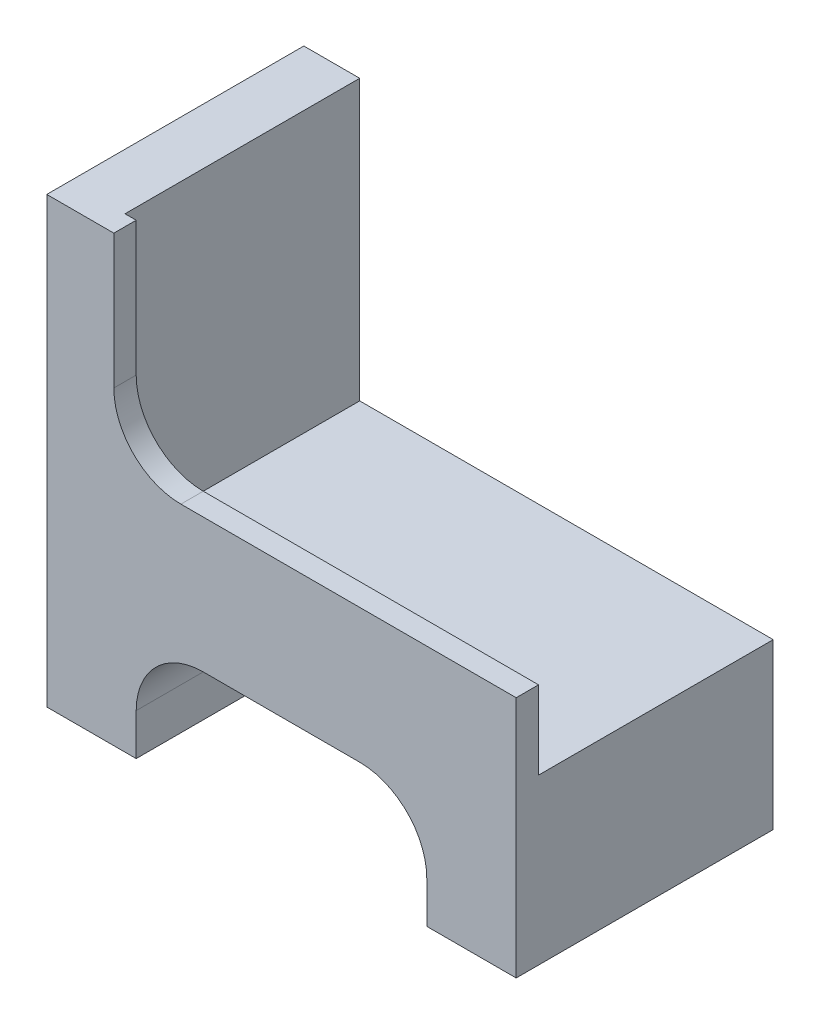
SolidWorks part; units mm, degrees
ref_plane "前视基准面" through (0, 0, 0) normal (0, 0, 1) x (1, 0, 0)
ref_plane "上视基准面" through (0, 0, 0) normal (0, 1, 0) x (1, 0, 0)
ref_plane "右视基准面" through (0, 0, 0) normal (1, 0, 0) x (0, 0, -1)
other "Configuration Table"
sketch "草图1" plane through (0, 0, 0) normal (0, 0, 1) x (1, 0, 0)
  line L0 (0, 0) -> (18, 0)
  line L1 (0, 0) -> (0, 12)
  line L2 (0, 12) -> (-3, 12)
  line L3 (-3, 12) -> (-3, -7.86)
  line L4 (1, -3) -> (14, -3)
  line L5 (18, -7.86) -> (18, 0)
  line L7 (-3, -7.86) -> (1, -7.86)
  line L8 (1, -7.86) -> (1, -3)
  line L10 (18, -7.86) -> (14, -7.86)
  line L11 (14, -7.86) -> (14, -3)
  point P3 (0, 0)
  point P7 (-3, -13.8907)
  point P13 (20, -13.8521)
  dimension "D1" = 3
  dimension "D2" = 4
  dimension "D3" = 12
  dimension "D4" = 18
  dimension "D5" = 4
  dimension "D6" = 3
  dimension "D7" = 4.86
extrude "凸台-拉伸1" add sketch "草图1" along normal blind 10
sketch "草图2" plane through (0, -7.86, 0) normal (0, -1, 0) x (1, 0, 0)
  line L0 (-1, 11.4054) -> (-1, -1.0148) construction
  line L1 (16, 11.2176) -> (16, -1.0148) construction
  line L2 (-3.4951, 5) -> (21.5595, 5) construction
  line L3 (14, 10) -> (18, 10) construction
  circle A0 centre (-1, 5) radius 0.95
  circle A1 centre (16, 5.1014) radius 0.95
  point P10 (-1, 5)
  point P11 (18, 5.1014)
  point P14 (16, 10)
  dimension "D1" = 1.9
  dimension "D2" = 1.9
extrude "切除-拉伸1" cut sketch "草图2" against normal blind 5
fillet "圆角1" radius 3 2 edges at (14, -3, 5) (1, -3, 5)
chamfer "倒角2" distance 1 angle 45 2 edges at (16.95, -7.86, 5.1014) (-0.05, -7.86, 5)
sketch "草图3" plane through (0, 0, 0) normal (0, 0, 1) x (1, 0, 0)
  point P0 (4, 6)
  point P4 (4, 6.9267)
  dimension "D1" = 4
  dimension "D2" = 6
ref_axis "电机轴" through (4, 6, 0) along (0, 0, 1)
sketch "草图4" plane through (0, 0, 10) normal (0, 0, 1) x (1, 0, 0)
  line L0 (0, 12) -> (0, 3)
  line L1 (0, 0) -> (0, 12) construction
  line L2 (0, 3) -> (18, 3)
  line L3 (18, 3) -> (18, 0)
  line L4 (18, 0) -> (0, 0) construction
  line L10 (0, 0) -> (0, 12)
  line L11 (0, 12) -> (-3, 12)
  line L12 (-3, 12) -> (-3, -7.86)
  line L13 (-3, -7.86) -> (1, -7.86)
  line L14 (1, -7.86) -> (1, -6)
  line L15 (4, -3) -> (11, -3)
  line L16 (14, -6) -> (14, -7.86)
  line L17 (14, -7.86) -> (18, -7.86)
  line L18 (18, -7.86) -> (18, 0)
  line L19 (18, 0) -> (0, 0)
  line L21 (0, 12) -> (-3, 12)
  line L22 (-3, 12) -> (-3, -7.86)
  line L23 (-3, -7.86) -> (1, -7.86)
  line L24 (1, -7.86) -> (1, -6)
  line L25 (4, -3) -> (11, -3)
  line L26 (14, -6) -> (14, -7.86)
  line L27 (14, -7.86) -> (18, -7.86)
  line L28 (18, -7.86) -> (18, 0)
  arc A2 (4, -3) -> (1, -6) centre (4, -6) ccw
  arc A3 (14, -6) -> (11, -3) centre (11, -6) ccw
  arc A4 (4, -3) -> (1, -6) centre (4, -6) ccw
  arc A5 (14, -6) -> (11, -3) centre (11, -6) ccw
  dimension "D2" = 3
  dimension "D1" = 0
extrude "凸台-拉伸2" add sketch "草图4" along normal blind 1.5
fillet "圆角2" radius 3 1 edges at (0, 3, 10.75)
sketch "草图5" plane through (0, 0, 0) normal (0, 0, -1) x (-1, 0, 0)
  line L0 (0, 0) -> (0, 12) construction
  line L1 (0.5, -0.5) -> (-18.3942, -0.5)
  line L2 (0.5, -0.5) -> (0.5, 13.0683)
  line L3 (0.5, 13.0683) -> (-18.3942, 13.0683)
  line L4 (-18.3942, -0.5) -> (-18.3942, 13.0683)
  line L5 (-18, 0) -> (0, 0) construction
  dimension "D1" = 0.5
  dimension "D2" = 0.5
extrude "游隙调整" cut sketch "草图5" against normal blind 10.5
